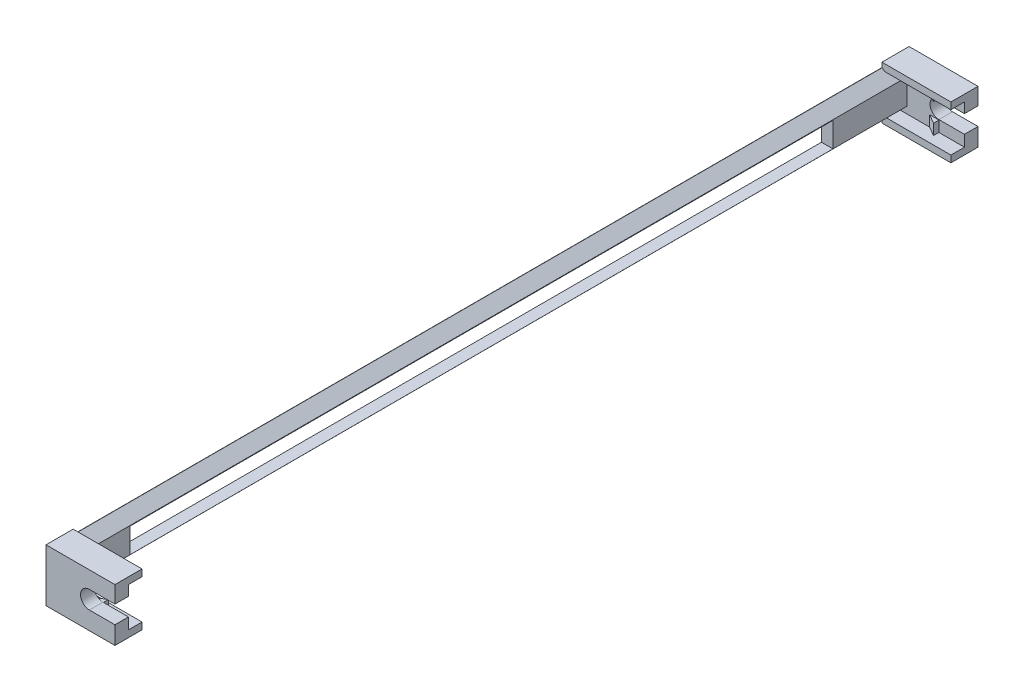
SolidWorks part; units mm, degrees
ref_plane "前视基准面" through (0, 0, 0) normal (0, 0, 1) x (1, 0, 0)
ref_plane "上视基准面" through (0, 0, 0) normal (0, 1, 0) x (1, 0, 0)
ref_plane "右视基准面" through (0, 0, 0) normal (1, 0, 0) x (0, 0, -1)
other "Configuration Table"
sketch "草图1" plane through (0, 0, 0) normal (0, 0, 1) x (1, 0, 0)
  line L1 (7.5293, 6.2547) -> (-12.8043, 6.2547)
  line L2 (7.5293, 6.2547) -> (7.5293, 2.63)
  line L3 (7.5293, -6.6238) -> (-12.8043, -6.6238)
  line L4 (-12.8043, 6.2547) -> (-12.8043, -6.6238)
  line L6 (0, 2.63) -> (7.5293, 2.63)
  line L7 (0, -2.63) -> (7.5293, -2.63)
  line L8 (7.5293, -2.63) -> (7.5293, -6.6238)
  arc A0 (-1.8597, -1.8597) -> (-1.8597, 1.8597) centre (0, 0) ccw construction
  arc A1 (0, 2.63) -> (0, -2.63) centre (0, 0) ccw
extrude "凸台-拉伸1" add sketch "草图1" along normal blind 4 from offset 0.3
sketch "草图2" plane through (0, 0, -246.3) normal (0, 0, -1) x (-1, 0, 0)
  line L7 (-7.5293, 6.2547) -> (-7.5293, 2.63)
  line L8 (-7.5293, 2.63) -> (0, 2.63)
  line L9 (0, -2.63) -> (-7.5293, -2.63)
  line L10 (-7.5293, -2.63) -> (-7.5293, -6.6238)
  line L11 (-7.5293, -6.6238) -> (12.8043, -6.6238)
  line L12 (12.8043, -6.6238) -> (12.8043, 6.2547)
  line L13 (12.8043, 6.2547) -> (-7.5293, 6.2547)
  line L14 (-7.5293, 6.2547) -> (-7.5293, 2.63)
  line L15 (-7.5293, 2.63) -> (0, 2.63)
  line L16 (0, -2.63) -> (-7.5293, -2.63)
  line L17 (-7.5293, -2.63) -> (-7.5293, -6.6238)
  line L18 (-7.5293, -6.6238) -> (12.8043, -6.6238)
  line L19 (12.8043, -6.6238) -> (12.8043, 6.2547)
  line L20 (12.8043, 6.2547) -> (-7.5293, 6.2547)
  arc A1 (0, -2.63) -> (0, 2.63) centre (0, 0) ccw
  arc A2 (0, -2.63) -> (0, 2.63) centre (0, 0) ccw
  dimension "D1" = 0
extrude "凸台-拉伸2" add sketch "草图2" along normal blind 4 separate body
sketch "草图3" plane through (-12.8043, 0, 0) normal (-1, 0, 0) x (0, 0, 1)
  line L0 (4.3, -6.6238) -> (0.3, -6.6238) construction
  line L1 (-250.3, 6.2547) -> (4.3, 6.2547)
  line L2 (-250.3, 6.2547) -> (-250.3, -6.6238)
  line L3 (-250.3, -6.6238) -> (4.3, -6.6238)
  line L4 (4.3, 6.2547) -> (4.3, -6.6238)
  line L5 (4.3, 6.2547) -> (4.3, -6.6238) construction
extrude "凸台-拉伸3" add sketch "草图3" against normal blind 3.4
sketch "草图4" plane through (-12.8043, 0, 0) normal (-1, 0, 0) x (0, 0, 1)
  line L0 (-224.3, 7.6754) -> (-224.3, -7.5563) construction
  line L1 (-224.3, 11.4857) -> (-224.3, 6.536) construction
  line L2 (-224.3, -6.8896) -> (-224.3, -11.8393) construction
  line L3 (-17.3, 7.3204) -> (-17.3, -8.473) construction
  line L4 (-224.45, 3.4) -> (-17.15, 3.4)
  line L5 (-224.45, 3.4) -> (-224.45, -3.9)
  line L6 (-224.45, -3.9) -> (-17.15, -3.9)
  line L7 (-17.15, 3.4) -> (-17.15, -3.9)
  line L8 (-17.3, 6.536) -> (-17.3, 11.4857) construction
  line L9 (-17.3, 3.25) -> (-224.3, 3.25) construction
  line L10 (-224.3, -3.75) -> (-17.3, -3.75) construction
  dimension "D1" = 0.15
  dimension "D2" = 0.15
  dimension "D3" = 0.15
  dimension "D4" = 0.15
extrude "切除-拉伸1" cut sketch "草图4" against normal up to next
sketch "草图5" plane through (0, 0, -246.3) normal (0, 0, 1) x (1, 0, 0)
  line L0 (7.5293, -6.6238) -> (-9.4043, -6.6238) construction
  line L1 (0, -6.6238) -> (-2.7458, -6.6238)
  line L2 (0, -6.6238) -> (0, -2.7646)
  line L3 (0, -2.7646) -> (-2.7458, -2.7646)
  line L4 (-2.7458, -6.6238) -> (-2.7458, -2.7646)
  line L5 (-9.4043, 6.2547) -> (7.5293, 6.2547) construction
  line L6 (0, 6.2547) -> (-2.7458, 6.2547)
  line L7 (0, 6.2547) -> (0, 2.8071)
  line L8 (0, 2.8071) -> (-2.7458, 2.8071)
  line L9 (-2.7458, 6.2547) -> (-2.7458, 2.8071)
extrude "凸台-拉伸4" add sketch "草图5" along normal blind 2
sketch "草图6" plane through (0, 0, 0.3) normal (0, 0, -1) x (-1, 0, 0)
  line L0 (0, -6.6238) -> (0, -2.7646) construction
  line L1 (0, -2.7646) -> (2.7458, -2.7646) construction
  line L2 (2.7458, -2.7646) -> (2.7458, -6.6238) construction
  line L3 (2.7458, -6.6238) -> (0, -6.6238) construction
  line L4 (0, 2.8071) -> (0, 6.2547) construction
  line L5 (0, 6.2547) -> (2.7458, 6.2547) construction
  line L6 (2.7458, 6.2547) -> (2.7458, 2.8071) construction
  line L7 (2.7458, 2.8071) -> (0, 2.8071) construction
  line L8 (0, -6.6238) -> (0, -2.7646)
  line L9 (0, -2.7646) -> (2.7458, -2.7646)
  line L10 (2.7458, -2.7646) -> (2.7458, -6.6238)
  line L11 (2.7458, -6.6238) -> (0, -6.6238)
  line L12 (0, 2.8071) -> (0, 6.2547)
  line L13 (0, 6.2547) -> (2.7458, 6.2547)
  line L14 (2.7458, 6.2547) -> (2.7458, 2.8071)
  line L15 (2.7458, 2.8071) -> (0, 2.8071)
extrude "凸台-拉伸5" add sketch "草图6" along normal blind 2
chamfer "倒角1" distance 2 angle 60 4 edges at (-2.7458, 4.5309, -244.3) (-2.7458, -4.6942, -244.3) (-2.7458, -4.6942, -1.7) (-2.7458, 4.5309, -1.7) first distance on face at (-2.7458, 4.5309, -245.3) first distance on face at (-2.7458, -4.6942, -245.3) first distance on face at (-2.7458, -4.6942, -0.7) first distance on face at (-2.7458, 4.5309, -0.7)
chamfer "倒角2" distance 2.7 angle 51 2 edges at (-9.4043, 6.2547, -123) (-9.4043, -6.6238, -123) first distance on face at (-9.4043, -0.25, -120.8)
sketch "草图7" plane through (0, 0, -246.3) normal (0, 0, 1) x (1, 0, 0)
  line L0 (7.5293, -2.63) -> (7.5293, -6.6238) construction
  line L1 (7.5293, -5.93) -> (-12.8043, -5.93)
  line L2 (7.5293, -5.93) -> (7.5293, -7.93)
  line L3 (7.5293, -7.93) -> (-12.8043, -7.93)
  line L4 (-12.8043, -5.93) -> (-12.8043, -7.93)
  line L5 (-12.8043, 6.2547) -> (-12.8043, -6.6238) construction
  line L6 (15, -5.63) -> (0, -5.63) construction
  line L12 (0, 5.63) -> (15, 5.63) construction
  line L13 (7.5293, 5.63) -> (-12.8043, 5.63)
  line L14 (7.5293, 5.63) -> (7.5293, 7.63)
  line L15 (7.5293, 7.63) -> (-12.8043, 7.63)
  line L16 (-12.8043, 5.63) -> (-12.8043, 7.63)
  line L17 (7.5293, 6.2547) -> (7.5293, 2.63) construction
  dimension "D1" = 2
  dimension "D2" = 0.3
  dimension "D3" = 2
extrude "凸台-拉伸6" add sketch "草图7" along normal blind 4 and the other way up to surface (4 mm away) other way up to face at (0.2348, -0.0923, -250.3)
sketch "草图8" plane through (0, 0, 0.3) normal (0, 0, -1) x (-1, 0, 0)
  line L6 (12.7385, -6.6238) -> (11.8817, -5.93)
  line L7 (12.8043, -6.6238) -> (12.7385, -6.6238)
  line L8 (12.8043, -7.93) -> (12.8043, -6.6238)
  line L9 (-7.5293, -7.93) -> (12.8043, -7.93)
  line L10 (-7.5293, -5.93) -> (-7.5293, -7.93)
  line L11 (11.8817, -5.93) -> (-7.5293, -5.93)
  line L12 (12.7385, -6.6238) -> (11.8817, -5.93)
  line L13 (12.8043, -6.6238) -> (12.7385, -6.6238)
  line L14 (12.8043, -7.93) -> (12.8043, -6.6238)
  line L15 (-7.5293, -7.93) -> (12.8043, -7.93)
  line L16 (-7.5293, -5.93) -> (-7.5293, -7.93)
  line L17 (11.8817, -5.93) -> (-7.5293, -5.93)
  line L30 (12.7385, 6.2547) -> (12.8043, 6.2547)
  line L31 (11.9671, 5.63) -> (12.7385, 6.2547)
  line L32 (-7.5293, 5.63) -> (11.9671, 5.63)
  line L33 (-7.5293, 7.63) -> (-7.5293, 5.63)
  line L34 (12.8043, 7.63) -> (-7.5293, 7.63)
  line L35 (12.8043, 6.2547) -> (12.8043, 7.63)
  line L36 (12.7385, 6.2547) -> (12.8043, 6.2547)
  line L37 (11.9671, 5.63) -> (12.7385, 6.2547)
  line L38 (-7.5293, 5.63) -> (11.9671, 5.63)
  line L39 (-7.5293, 7.63) -> (-7.5293, 5.63)
  line L40 (12.8043, 7.63) -> (-7.5293, 7.63)
  line L41 (12.8043, 6.2547) -> (12.8043, 7.63)
  dimension "D1" = 0
  dimension "D2" = 0
extrude "凸台-拉伸7" add sketch "草图8" along normal blind 4 and the other way up to surface (4 mm away) other way up to face at (0.2348, -0.0923, 4.3)
sketch "草图9" plane through (0, 0, -250.3) normal (0, 0, -1) x (-1, 0, 0)
  line L0 (0, 0) -> (12.8043, 0)
  line L5 (12.8043, 7.63) -> (12.8043, -7.93) construction
  point P4 (0, 0)
  point P5 (0, 0)
extrude "切除-拉伸-薄壁1" cut sketch "草图9" against normal blind 1 and the other way through all thin thin type mid plane wall 1
